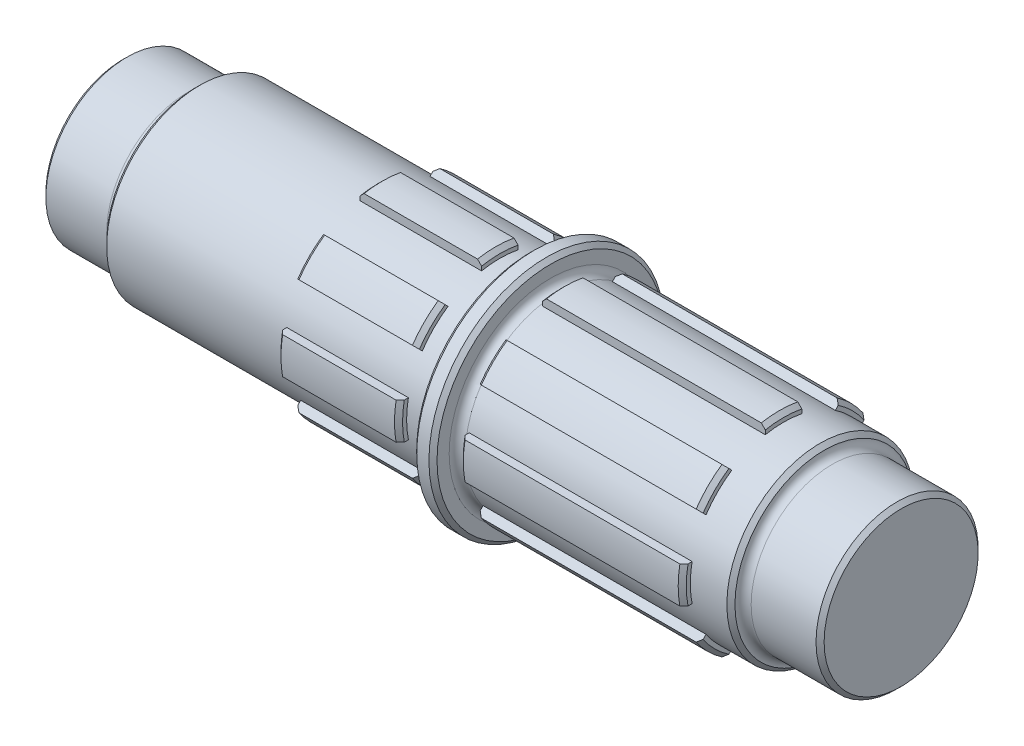
SolidWorks part; units mm, degrees
ref_plane "Front Plane" through (0, 0, 0) normal (0, 0, 1) x (1, 0, 0)
ref_plane "Top Plane" through (0, 0, 0) normal (0, 1, 0) x (1, 0, 0)
ref_plane "Right Plane" through (0, 0, 0) normal (1, 0, 0) x (0, 0, -1)
sketch "Sketch1" plane through (0, 0, 0) normal (0, 0, 1) x (1, 0, 0)
  line L0 (-133.4132, 0) -> (155.2096, 0) construction
  line L1 (-119.2814, 0) -> (-119.2814, 20)
  line L2 (-119.2814, 20) -> (-101.2814, 20)
  line L3 (-101.2814, 20) -> (-101.2814, 23)
  line L4 (-101.2814, 23) -> (-56.2814, 23)
  line L5 (-18.7814, 23) -> (-18.7814, 29)
  line L6 (-18.7814, 29) -> (-13.7814, 29)
  line L7 (-13.7814, 29) -> (-13.7814, 23)
  line L8 (-13.7814, 23) -> (-11.2814, 23)
  line L9 (53.7186, 23) -> (53.7186, 20)
  line L10 (53.7186, 20) -> (72.7186, 20)
  line L11 (72.7186, 20) -> (72.7186, 0)
  line L12 (-56.2814, 23) -> (-56.2814, 25)
  line L13 (-56.2814, 25) -> (-26.2814, 25)
  line L14 (-26.2814, 25) -> (-26.2814, 23)
  line L15 (-26.2814, 23) -> (-18.7814, 23)
  line L16 (-11.2814, 23) -> (-11.2814, 25)
  line L17 (-11.2814, 25) -> (43.7186, 25)
  line L18 (43.7186, 25) -> (43.7186, 23)
  line L19 (43.7186, 23) -> (53.7186, 23)
  line L20 (-119.2814, 0) -> (72.7186, 0)
  point P5 (-41.2814, 23)
  point P18 (16.2186, 23)
  dimension "D1" = 20
  dimension "D2" = 20
  dimension "D3" = 46
  dimension "D4" = 46
  dimension "D5" = 58
  dimension "D6" = 5
  dimension "D7" = 82.5
  dimension "D8" = 67.5
  dimension "D9" = 18
  dimension "D10" = 19
  dimension "D11" = 60
  dimension "D12" = 15
  dimension "D13" = 15
  dimension "D14" = 50
  dimension "D15" = 37.5
  dimension "D16" = 27.5
  dimension "D17" = 27.5
  dimension "D18" = 50
revolve "Revolve1" add sketch "Sketch1" angle 360 about L0
chamfer "Chamfer1" distance 1 angle 45 9 edges at (72.7186, 0, 20) (53.7186, 0, 23) (43.7186, 0, 25) (-13.7814, 0, 29) (-18.7814, 0, 29) (-26.2814, 0, 25) (-56.2814, 0, 25) (-101.2814, 0, 23) (-119.2814, 0, 20)
sketch "Sketch2" plane through (-56.2814, 0, 0) normal (-1, 0, 0) x (0, 0, 1)
  line L0 (0, 0) -> (0, 29.8061) construction
  line L1 (-4.5, 24.5917) -> (-4.5, 22.5555)
  line L2 (4.5, 24.5917) -> (4.5, 22.5555)
  line L3 (14.207, 20.5709) -> (12.7672, 19.1311)
  line L4 (20.5709, 14.207) -> (19.1311, 12.7672)
  line L5 (24.5917, 4.5) -> (22.5555, 4.5)
  line L6 (24.5917, -4.5) -> (22.5555, -4.5)
  line L7 (20.5709, -14.207) -> (19.1311, -12.7672)
  line L8 (14.207, -20.5709) -> (12.7672, -19.1311)
  line L9 (4.5, -24.5917) -> (4.5, -22.5555)
  line L10 (-4.5, -24.5917) -> (-4.5, -22.5555)
  line L11 (-14.207, -20.5709) -> (-12.7672, -19.1311)
  line L12 (-20.5709, -14.207) -> (-19.1311, -12.7672)
  line L13 (-24.5917, -4.5) -> (-22.5555, -4.5)
  line L14 (-24.5917, 4.5) -> (-22.5555, 4.5)
  line L15 (-20.5709, 14.207) -> (-19.1311, 12.7672)
  line L16 (-14.207, 20.5709) -> (-12.7672, 19.1311)
  circle A0 centre (0, 0) radius 25 construction
  circle A1 centre (0, 0) radius 23 construction
  arc A2 (-20.5709, 14.207) -> (-24.5917, 4.5) centre (0, 0) ccw
  arc A3 (-19.1311, 12.7672) -> (-22.5555, 4.5) centre (0, 0) ccw
  arc A4 (-24.5917, -4.5) -> (-20.5709, -14.207) centre (0, 0) ccw
  arc A5 (-22.5555, -4.5) -> (-19.1311, -12.7672) centre (0, 0) ccw
  arc A6 (-14.207, -20.5709) -> (-4.5, -24.5917) centre (0, 0) ccw
  arc A7 (-12.7672, -19.1311) -> (-4.5, -22.5555) centre (0, 0) ccw
  arc A8 (4.5, -24.5917) -> (14.207, -20.5709) centre (0, 0) ccw
  arc A9 (4.5, -22.5555) -> (12.7672, -19.1311) centre (0, 0) ccw
  arc A10 (20.5709, -14.207) -> (24.5917, -4.5) centre (0, 0) ccw
  arc A11 (19.1311, -12.7672) -> (22.5555, -4.5) centre (0, 0) ccw
  arc A12 (24.5917, 4.5) -> (20.5709, 14.207) centre (0, 0) ccw
  arc A13 (22.5555, 4.5) -> (19.1311, 12.7672) centre (0, 0) ccw
  arc A14 (14.207, 20.5709) -> (4.5, 24.5917) centre (0, 0) ccw
  arc A15 (12.7672, 19.1311) -> (4.5, 22.5555) centre (0, 0) ccw
  arc A16 (-4.5, 24.5917) -> (-14.207, 20.5709) centre (0, 0) ccw
  arc A17 (-4.5, 22.5555) -> (-12.7672, 19.1311) centre (0, 0) ccw
  point P42 (0, 0)
  dimension "D1" = 4.5
  dimension "D2" = 8
extrude "Cut-Extrude1" cut sketch "Sketch2" against normal up to surface (30 mm away) up to face at (-26.2814, 0, 24)
chamfer "Chamfer2" distance 1 angle 45 1 edges at (-11.2814, 0, 25)
sketch "Sketch4" plane through (43.7186, 0, 0) normal (1, 0, 0) x (0, 0, -1)
  line L0 (0, 0) -> (0, 34.03) construction
  line L1 (-4.5, 24.5917) -> (-4.5, 22.5555)
  line L2 (4.5, 24.5917) -> (4.5, 22.5555)
  line L3 (14.207, 20.5709) -> (12.7672, 19.1311)
  line L4 (20.5709, 14.207) -> (19.1311, 12.7672)
  line L5 (24.5917, 4.5) -> (22.5555, 4.5)
  line L6 (24.5917, -4.5) -> (22.5555, -4.5)
  line L7 (20.5709, -14.207) -> (19.1311, -12.7672)
  line L8 (14.207, -20.5709) -> (12.7672, -19.1311)
  line L9 (4.5, -24.5917) -> (4.5, -22.5555)
  line L10 (-4.5, -24.5917) -> (-4.5, -22.5555)
  line L11 (-14.207, -20.5709) -> (-12.7672, -19.1311)
  line L12 (-20.5709, -14.207) -> (-19.1311, -12.7672)
  line L13 (-24.5917, -4.5) -> (-22.5555, -4.5)
  line L14 (-24.5917, 4.5) -> (-22.5555, 4.5)
  line L15 (-20.5709, 14.207) -> (-19.1311, 12.7672)
  line L16 (-14.207, 20.5709) -> (-12.7672, 19.1311)
  circle A0 centre (0, 0) radius 25 construction
  circle A1 centre (0, 0) radius 23 construction
  arc A2 (-20.5709, 14.207) -> (-24.5917, 4.5) centre (0, 0) ccw
  arc A3 (-19.1311, 12.7672) -> (-22.5555, 4.5) centre (0, 0) ccw
  arc A4 (-4.5, 24.5917) -> (-14.207, 20.5709) centre (0, 0) ccw
  arc A5 (-4.5, 22.5555) -> (-12.7672, 19.1311) centre (0, 0) ccw
  arc A6 (14.207, 20.5709) -> (4.5, 24.5917) centre (0, 0) ccw
  arc A7 (12.7672, 19.1311) -> (4.5, 22.5555) centre (0, 0) ccw
  arc A8 (24.5917, 4.5) -> (20.5709, 14.207) centre (0, 0) ccw
  arc A9 (22.5555, 4.5) -> (19.1311, 12.7672) centre (0, 0) ccw
  arc A10 (19.1311, -12.7672) -> (22.5555, -4.5) centre (0, 0) ccw
  arc A11 (20.5709, -14.207) -> (24.5917, -4.5) centre (0, 0) ccw
  arc A12 (4.5, -22.5555) -> (12.7672, -19.1311) centre (0, 0) ccw
  arc A13 (4.5, -24.5917) -> (14.207, -20.5709) centre (0, 0) ccw
  arc A14 (-12.7672, -19.1311) -> (-4.5, -22.5555) centre (0, 0) ccw
  arc A15 (-14.207, -20.5709) -> (-4.5, -24.5917) centre (0, 0) ccw
  arc A16 (-22.5555, -4.5) -> (-19.1311, -12.7672) centre (0, 0) ccw
  arc A17 (-24.5917, -4.5) -> (-20.5709, -14.207) centre (0, 0) ccw
  point P41 (0, 0)
  dimension "D1" = 4.5
extrude "Cut-Extrude3" cut sketch "Sketch4" against normal up to surface (55 mm away) up to face at (-11.2814, 0, -24)
fillet "Fillet1" radius 2 4 edges at (53.7186, 0, 20) (-13.7814, 0, 23) (-18.7814, 0, 23) (-101.2814, 0, 20)
